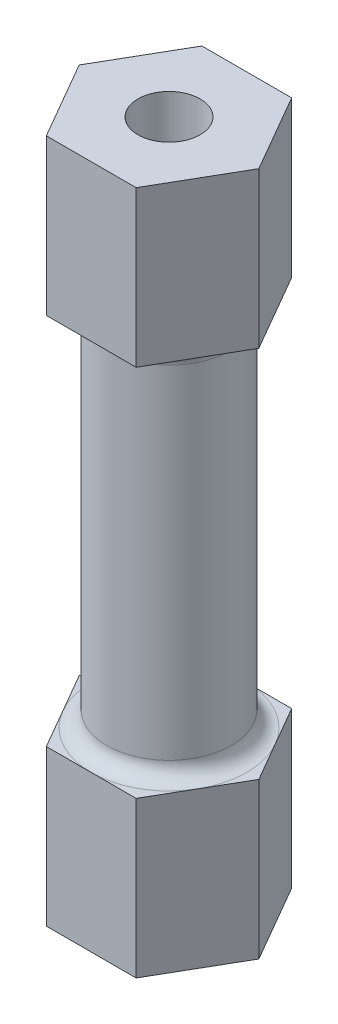
SolidWorks part; units mm, degrees
ref_plane "Front Plane" through (0, 0, 0) normal (0, 0, 1) x (1, 0, 0)
ref_plane "Top Plane" through (0, 0, 0) normal (0, 1, 0) x (1, 0, 0)
ref_plane "Right Plane" through (0, 0, 0) normal (1, 0, 0) x (0, 0, -1)
sketch "Sketch1" plane through (0, 0, 0) normal (0, 1, 0) x (1, 0, 0)
  line L1 (2.8868, 0) -> (1.4434, 2.5)
  line L2 (1.4434, 2.5) -> (-1.4434, 2.5)
  line L3 (-1.4434, 2.5) -> (-2.8868, 0)
  line L4 (-2.8868, 0) -> (-1.4434, -2.5)
  line L5 (-1.4434, -2.5) -> (1.4434, -2.5)
  line L6 (1.4434, -2.5) -> (2.8868, 0)
  circle A0 centre (0, 0) radius 2.5 construction
  dimension "D1" = 5
extrude "Boss-Extrude1" add sketch "Sketch1" along normal blind 5
sketch "Sketch2" plane through (0, 5, 0) normal (0, 1, 0) x (1, 0, 0)
  circle A0 centre (0, 0) radius 2
extrude "Boss-Extrude2" add sketch "Sketch2" along normal blind 12
sketch "Sketch3" plane through (0, 17, 0) normal (0, 1, 0) x (1, 0, 0)
  line L1 (2.8868, 0) -> (1.4434, 2.5)
  line L2 (1.4434, 2.5) -> (-1.4434, 2.5)
  line L3 (-1.4434, 2.5) -> (-2.8868, 0)
  line L4 (-2.8868, 0) -> (-1.4434, -2.5)
  line L5 (-1.4434, -2.5) -> (1.4434, -2.5)
  line L6 (1.4434, -2.5) -> (2.8868, 0)
  circle A0 centre (0, 0) radius 2.5 construction
extrude "Boss-Extrude3" add sketch "Sketch3" along normal blind 5
fillet "Fillet3" radius 0.5 2 edges at (0, 17, 2) (0, 5, 2)
sketch "Sketch4" plane through (0, 0, 0) normal (0, -1, 0) x (1, 0, 0)
  circle A0 centre (0, 0) radius 1
extrude "Cut-Extrude1" cut sketch "Sketch4" against normal through all
